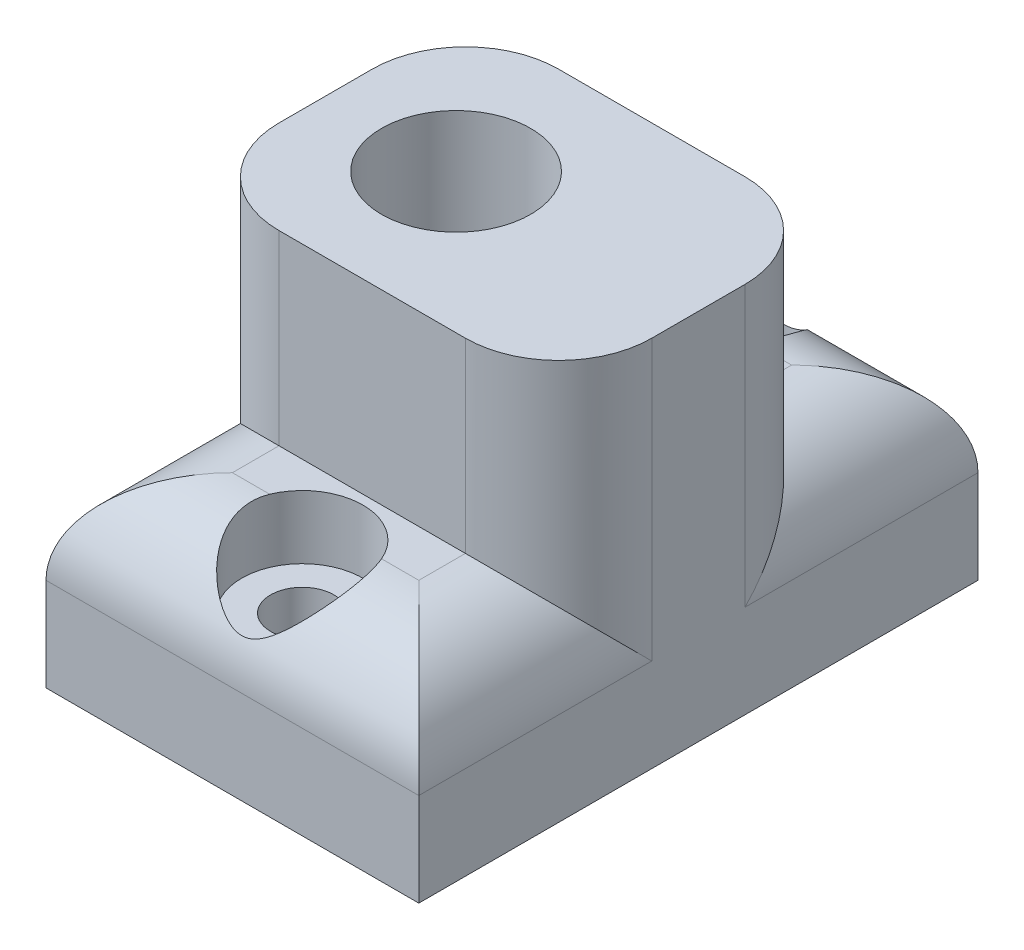
SolidWorks part; units mm, degrees
material "ABS"
ref_plane "Front Plane" through (0, 0, 0) normal (0, 0, 1) x (1, 0, 0)
ref_plane "Top Plane" through (0, 0, 0) normal (0, 1, 0) x (1, 0, 0)
ref_plane "Right Plane" through (0, 0, 0) normal (1, 0, 0) x (0, 0, -1)
sketch "Sketch1" plane through (0, 0, 0) normal (0, 1, 0) x (1, 0, 0)
  line L1 (-10, -15) -> (10, -15)
  line L2 (-10, -15) -> (-10, 15)
  line L3 (-10, 15) -> (10, 15)
  line L4 (10, -15) -> (10, 15)
  line L5 (-10, -15) -> (10, 15) construction
  line L6 (-10, 15) -> (10, -15) construction
  point P1 (0, 0)
  dimension "D1" = 20
  dimension "D2" = 30
extrude "Boss-Extrude1" add sketch "Sketch1" along normal blind 20
sketch "Sketch2" plane through (0, 20, 0) normal (0, 1, 0) x (1, 0, 0)
  line L0 (-10, 15) -> (-10, -15) construction
  circle A0 centre (-3, 0) radius 4
  dimension "D2" = 8
  dimension "D1" = 7
extrude "Cut-Extrude1" cut sketch "Sketch2" against normal blind 10
sketch "Sketch3" plane through (0, 20, 0) normal (0, 1, 0) x (1, 0, 0)
  line L0 (10, -15) -> (10, 15) construction
  line L1 (-10, -15) -> (10, -15)
  line L2 (-10, -15) -> (-10, -7.5)
  line L3 (-10, -7.5) -> (10, -7.5)
  line L4 (10, -15) -> (10, -7.5)
  line L6 (-10, 15) -> (10, 15)
  line L7 (-10, 15) -> (-10, 7.5)
  line L8 (-10, 7.5) -> (10, 7.5)
  line L9 (10, 15) -> (10, 7.5)
  dimension "D1" = 7.5
  dimension "D2" = 7.5
extrude "Cut-Extrude2" cut sketch "Sketch3" against normal blind 10
hole_wizard "CBORE for M3 Hex Socket Head Cap Screw1" positions "Sketch4" profile "Sketch5" counterbore size "M3" standard "ISO" end condition through all
sketch "Sketch4" plane through (0, 10, 0) normal (0, 1, 0) x (1, 0, 0)
  line L1 (-10, -15) -> (10, -15) construction
  line L2 (10, 15) -> (-10, 15) construction
  point P0 (0, -11.25)
  point P2 (0, 11.25)
  dimension "D1" = 3.75
  dimension "D2" = 3.75
sketch "Sketch5" plane through (0, 10, 11.25) normal (1, 0, 0) x (0, 0, 1)
  line L0 (0, 0) -> (0, 10)
  line L1 (0, 10) -> (1.7, 10)
  line L3 (1.7, 10) -> (1.7, 3.4)
  line L4 (1.7, 3.4) -> (3.25, 3.4)
  line L5 (3.25, 3.4) -> (3.25, 0)
  line L7 (3.25, 0) -> (0, 0)
  line L11 (0, -6.35) -> (0, 107.95) construction
  dimension "Thru Hole Dia." = 3.4
  dimension "Thru Hole Depth" = 10
  dimension "C'Bore Dia." = 6.5
  dimension "C'Bore Depth" = 3.4
fillet "Fillet2" radius 5 10 edges at (0, 10, 15) (-10, 10, 11.25) (-10, 10, -11.25) (0, 10, -15) (10, 10, -11.25) (10, 10, 11.25) (-10, 15, -7.5) (-10, 15, 7.5) (10, 15, -7.5) (10, 15, 7.5)
